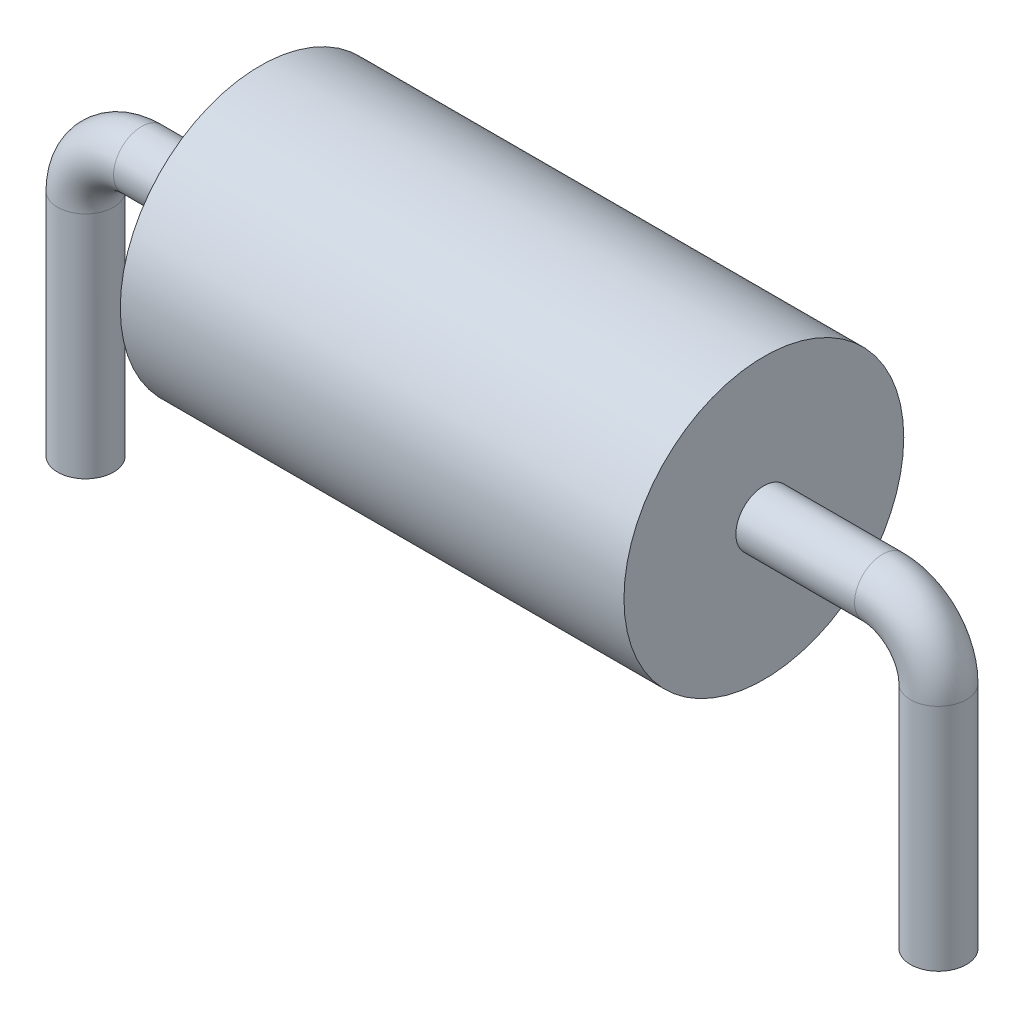
SolidWorks part; units mm, degrees
ref_plane "Спереди" through (0, 0, 0) normal (0, 0, 1) x (1, 0, 0)
ref_plane "Сверху" through (0, 0, 0) normal (0, 1, 0) x (1, 0, 0)
ref_plane "Справа" through (0, 0, 0) normal (1, 0, 0) x (0, 0, -1)
sketch "Эскиз1" plane through (0, 0, 0) normal (1, 0, 0) x (0, 0, -1)
  circle A0 centre (0, 0) radius 2.5
extrude "Бобышка-Вытянуть1" add sketch "Эскиз1" along normal blind 4.5 and the other way blind 4.5
sketch "Эскиз2" plane through (0, 0, 0) normal (0, 0, 1) x (1, 0, 0)
  line L0 (-6.62, 0) -> (6.62, 0)
  line L1 (7.62, -1) -> (7.62, -5.1)
  line L2 (0, -50) -> (0, 50) construction
  line L3 (-7.62, -1) -> (-7.62, -5.1)
  arc A0 (6.62, 0) -> (7.62, -1) centre (6.62, -1) cw
  arc A1 (-6.62, 0) -> (-7.62, -1) centre (-6.62, -1) ccw
  point P8 (0, 0)
  point P9 (7.62, 0)
  point P11 (0, 0)
  dimension "D2" = 1
  dimension "D1" = 7.62
  dimension "D3" = 5.1
sketch "Эскиз3" plane through (4.5, 0, 0) normal (1, 0, 0) x (0, 0, -1)
  circle A0 centre (0, 0) radius 0.5
sweep "По траектории1" add profiles "Эскиз3" path "Эскиз2"
